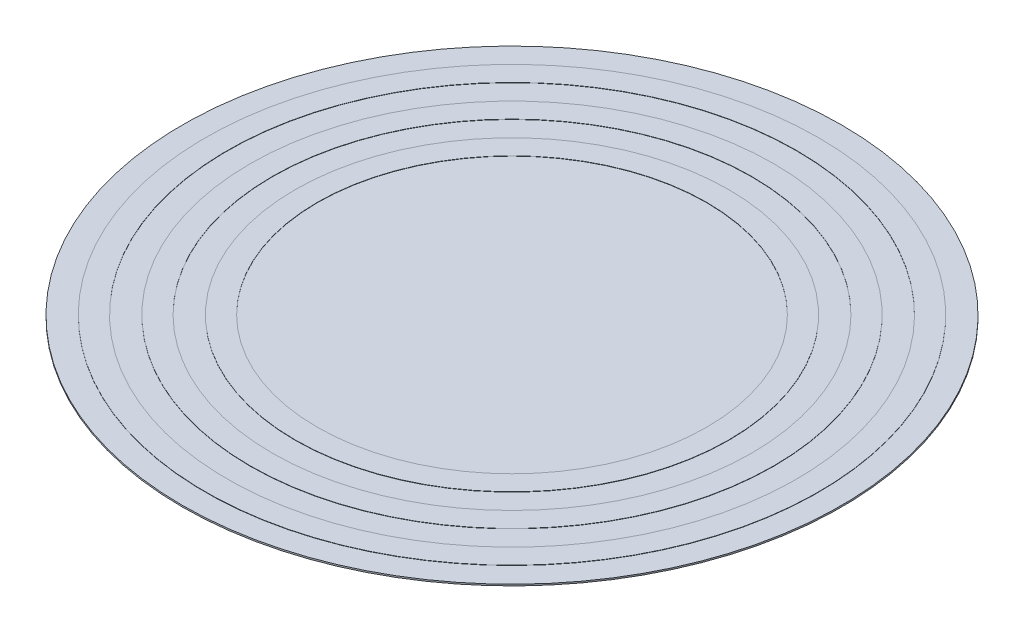
SolidWorks part; units mm, degrees
material "ABS"
ref_plane "Front Plane" through (0, 0, 0) normal (0, 0, 1) x (1, 0, 0)
ref_plane "Top Plane" through (0, 0, 0) normal (0, 1, 0) x (1, 0, 0)
ref_plane "Right Plane" through (0, 0, 0) normal (1, 0, 0) x (0, 0, -1)
sketch "Sketch1" plane through (0, 0, 0) normal (0, 1, 0) x (1, 0, 0)
  circle A0 centre (0, 0) radius 11
  dimension "D1" = 22
extrude "Boss-Extrude1" add sketch "Sketch1" along normal blind 0.05
sketch "Sketch2" plane through (0, 0.05, 0) normal (0, 1, 0) x (1, 0, 0)
  circle A0 centre (0, 0) radius 9.5
  dimension "D1" = 19
extrude "Extrude-Thin2" add sketch "Sketch2" along normal blind 0.01 separate body thin thin type one direction wall 0.7366
sketch "Sketch17" plane through (0, 0.05, 0) normal (0, 1, 0) x (1, 0, 0)
  circle A0 centre (0, 0) radius 8
  point P3 (0, 0)
  dimension "D1" = 16
extrude "Extrude-Thin3" add sketch "Sketch17" along normal blind 0.01 thin thin type one direction wall 0.7366
sketch "Sketch18" plane through (0, 0.05, 0) normal (0, 1, 0) x (1, 0, 0)
  circle A0 centre (0, 0) radius 6.5
  dimension "D1" = 13
extrude "Extrude-Thin4" add sketch "Sketch18" along normal blind 0.01 thin thin type one direction wall 0.7366
